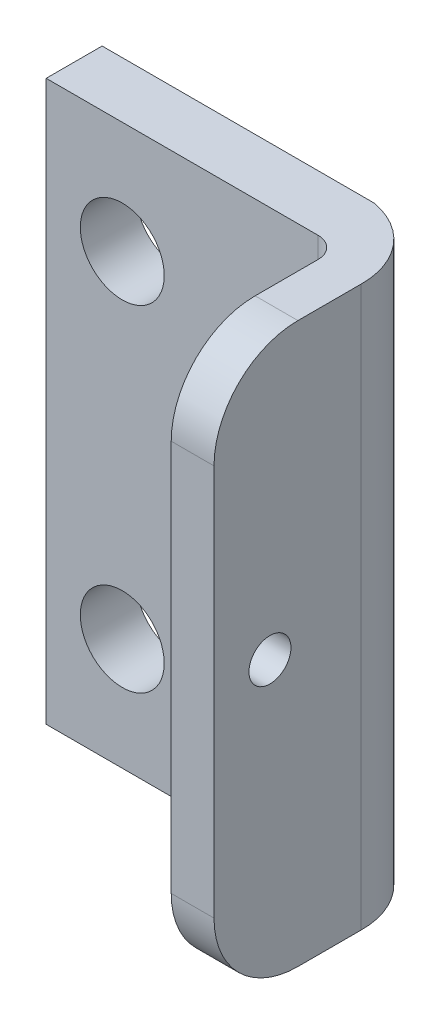
SolidWorks part; units mm, degrees
ref_plane "Front Plane" through (0, 0, 0) normal (0, 0, 1) x (1, 0, 0)
ref_plane "Top Plane" through (0, 0, 0) normal (0, 1, 0) x (1, 0, 0)
ref_plane "Right Plane" through (0, 0, 0) normal (1, 0, 0) x (0, 0, -1)
sketch "Sketch1" plane through (0, 0, 0) normal (0, 0, 1) x (1, 0, 0)
  line L1 (0, 0) -> (9.72, 0)
  line L2 (0, 0) -> (0, 20)
  line L3 (0, 20) -> (9.72, 20)
  line L4 (9.72, 0) -> (9.72, 20)
  line L5 (4.86, 20) -> (4.86, 0) construction
  line L6 (0, 10) -> (9.72, 10) construction
  circle A0 centre (2.72, 16) radius 1.5
  circle A1 centre (2.72, 4) radius 1.5
  point P8 (0, 0)
  point P9 (0, 0)
  point P10 (0, 0)
  point P380 (4.86, 10)
  dimension "D2" = 3
  dimension "D3" = 3
  dimension "D1" = 20
  dimension "D4" = 4
  dimension "D5" = 4
  dimension "D6" = 2.72
  dimension "D7" = 7
extrude "Boss-Extrude1" add sketch "Sketch1" along normal blind 2
sketch "Sketch2" plane through (0, 0, 0) normal (0, -1, 0) x (1, 0, 0)
  line L0 (9.72, 2) -> (9.72, 0)
  line L1 (11.9997, 2.75) -> (10.47, 2.75)
  line L2 (0, 2) -> (9.72, 2) construction
  arc A0 (9.72, 0) -> (11.9997, 2.75) centre (9.25, 2.7095) ccw
  arc A2 (9.72, 2) -> (10.47, 2.75) centre (9.72, 2.75) ccw
  point P11 (9.72, 4.2453)
  point P12 (0, 0)
  point P14 (0, 0)
  dimension "D1" = 5.5
  dimension "D3" = 1.5
  dimension "D2" = 0.47
  dimension "D4" = 0.75
  dimension "D5" = 0.75
extrude "Boss-Extrude2" add sketch "Sketch2" against normal blind 20
ref_plane "Plane1" through (12, 0, 0) normal (1, 0, 0) x (0, 0, -1)
sketch "Sketch3" plane through (12, 0, 0) normal (1, 0, 0) x (0, 0, -1)
  line L0 (-2.75, 20) -> (-5, 20)
  line L1 (-8, 17) -> (-8, 3)
  line L2 (-5, 0) -> (-2.75, 0)
  line L3 (-2.75, 20) -> (-2.75, 0)
  line L4 (0, 0) -> (0, 20) construction
  arc A0 (-8, 3) -> (-5, 0) centre (-5, 3) ccw
  arc A1 (-5, 20) -> (-8, 17) centre (-5, 17) ccw
  circle A2 centre (-6, 10) radius 0.75
  dimension "D2" = 3
  dimension "D3" = 1.5
  dimension "D1" = 8
  dimension "D4" = 2
  dimension "D5" = 10
extrude "Boss-Extrude3" add sketch "Sketch3" against normal up to vertex (1.53 mm away) up to point (10.47, 0, 2.75)
